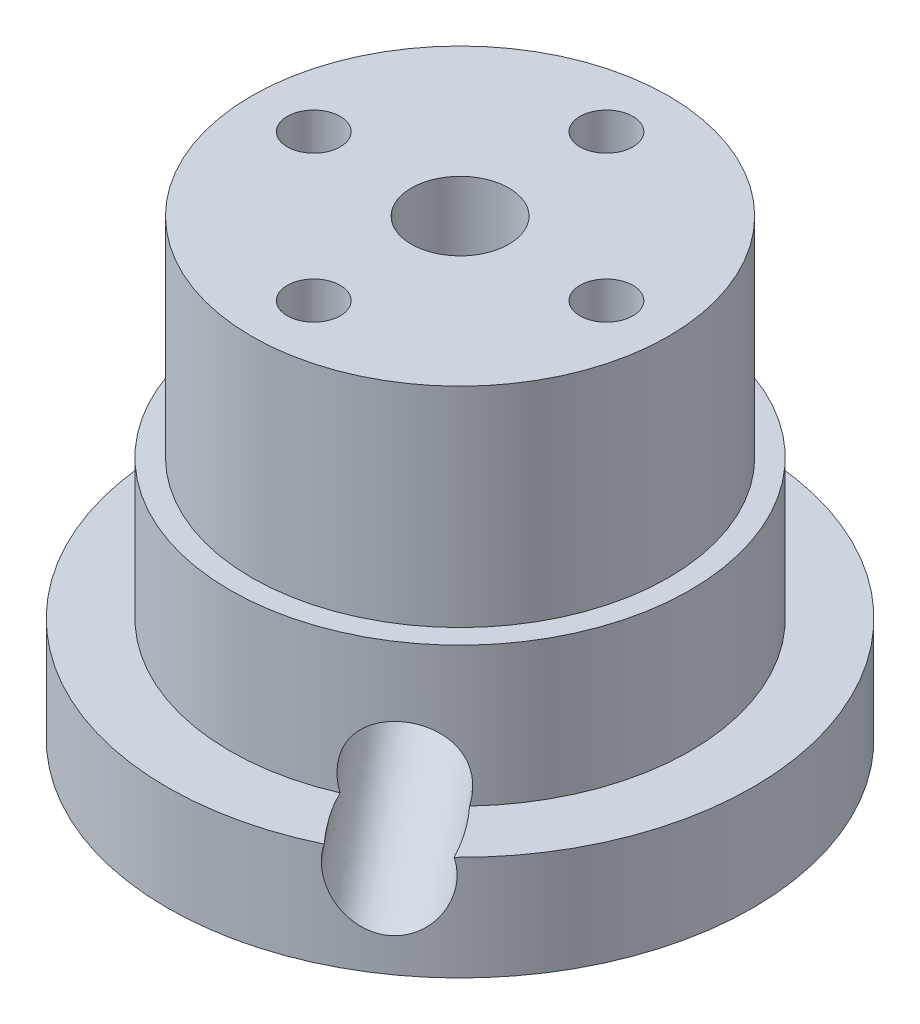
SolidWorks part; units mm, degrees
ref_plane "Alzado" through (0, 0, 0) normal (0, 0, 1) x (1, 0, 0)
ref_plane "Planta" through (0, 0, 0) normal (0, 1, 0) x (1, 0, 0)
ref_plane "Vista lateral" through (0, 0, 0) normal (1, 0, 0) x (0, 0, -1)
sketch "Croquis1" plane through (0, 0, 0) normal (0, 1, 0) x (1, 0, 0)
  circle A0 centre (0, 0) radius 21
  dimension "D1" = 42
extrude "Saliente-Extruir1" add sketch "Croquis1" along normal blind 7.5
sketch "Croquis2" plane through (0, 7.5, 0) normal (0, 1, 0) x (1, 0, 0)
  circle A0 centre (0, 0) radius 14.95
  dimension "D1" = 29.9
extrude "Saliente-Extruir2" add sketch "Croquis2" along normal blind 25
sketch "Croquis3" plane through (0, 0, 0) normal (0, -1, 0) x (1, 0, 0)
  line L0 (4, -5.5) -> (4, -8.4192) construction
  line L1 (-5.5, -4) -> (-8.4192, -4) construction
  line L2 (-4, -5.5) -> (-4, -8.4192) construction
  line L3 (-4, -8.4192) -> (-2.468, -17.8989) construction
  line L4 (4, -8.4192) -> (2.468, -17.8989) construction
  line L5 (5.5, -4) -> (8.4192, -4) construction
  line L6 (8.4192, -4) -> (17.8989, -2.468) construction
  line L7 (8.4192, 4) -> (17.8989, 2.468) construction
  line L8 (5.5, 4) -> (8.4192, 4) construction
  line L9 (4, 5.5) -> (4, 8.4192) construction
  line L10 (4, 8.4192) -> (2.468, 17.8989) construction
  line L11 (-4, 8.4192) -> (-2.468, 17.8989) construction
  line L12 (-4, 5.5) -> (-4, 8.4192) construction
  line L13 (-5.5, 4) -> (-8.4192, 4) construction
  line L14 (-8.4192, 4) -> (-17.8989, 2.468) construction
  line L15 (-8.4192, -4) -> (-17.8989, -2.468) construction
  line L16 (4, -5.5) -> (4, -8.4192) construction
  line L17 (-5.5, -4) -> (-8.4192, -4) construction
  line L18 (-4, -5.5) -> (-4, -8.4192) construction
  line L19 (-4, -8.4192) -> (-2.468, -17.8989) construction
  line L20 (4, -8.4192) -> (2.468, -17.8989) construction
  line L21 (5.5, -4) -> (8.4192, -4) construction
  line L22 (8.4192, -4) -> (17.8989, -2.468) construction
  line L23 (8.4192, 4) -> (17.8989, 2.468) construction
  line L24 (5.5, 4) -> (8.4192, 4) construction
  line L25 (4, 5.5) -> (4, 8.4192) construction
  line L26 (4, 8.4192) -> (2.468, 17.8989) construction
  line L27 (-4, 8.4192) -> (-2.468, 17.8989) construction
  line L28 (-4, 5.5) -> (-4, 8.4192) construction
  line L29 (-5.5, 4) -> (-8.4192, 4) construction
  line L30 (-8.4192, 4) -> (-17.8989, 2.468) construction
  line L31 (-8.4192, -4) -> (-17.8989, -2.468) construction
  line L32 (4.2, -5.5) -> (4.2, -8.4352)
  line L33 (4.2, -8.4352) -> (2.6654, -17.9308)
  line L34 (-4.2, -8.4352) -> (-2.6654, -17.9308)
  line L35 (-4.2, -5.5) -> (-4.2, -8.4352)
  line L36 (-5.5, -4.2) -> (-8.4352, -4.2)
  line L37 (-8.4352, -4.2) -> (-17.9308, -2.6654)
  line L38 (-8.4352, 4.2) -> (-17.9308, 2.6654)
  line L39 (-5.5, 4.2) -> (-8.4352, 4.2)
  line L40 (-4.2, 5.5) -> (-4.2, 8.4352)
  line L41 (-4.2, 8.4352) -> (-2.6654, 17.9308)
  line L42 (4.2, 8.4352) -> (2.6654, 17.9308)
  line L43 (4.2, 5.5) -> (4.2, 8.4352)
  line L44 (5.5, 4.2) -> (8.4352, 4.2)
  line L45 (8.4352, 4.2) -> (17.9308, 2.6654)
  line L46 (8.4352, -4.2) -> (17.9308, -2.6654)
  line L47 (5.5, -4.2) -> (8.4352, -4.2)
  arc A0 (-4, -5.5) -> (-5.5, -4) centre (-5.5, -5.5) ccw construction
  arc A1 (-2.468, -17.8989) -> (2.468, -17.8989) centre (0, -17.5) ccw construction
  arc A2 (5.5, -4) -> (4, -5.5) centre (5.5, -5.5) ccw construction
  arc A3 (17.8989, -2.468) -> (17.8989, 2.468) centre (17.5, 0) ccw construction
  arc A4 (4, 5.5) -> (5.5, 4) centre (5.5, 5.5) ccw construction
  arc A5 (2.468, 17.8989) -> (-2.468, 17.8989) centre (0, 17.5) ccw construction
  arc A6 (-5.5, 4) -> (-4, 5.5) centre (-5.5, 5.5) ccw construction
  arc A7 (-17.8989, 2.468) -> (-17.8989, -2.468) centre (-17.5, 0) ccw construction
  arc A8 (-4, -5.5) -> (-5.5, -4) centre (-5.5, -5.5) ccw construction
  arc A9 (-2.468, -17.8989) -> (2.468, -17.8989) centre (0, -17.5) ccw construction
  arc A10 (5.5, -4) -> (4, -5.5) centre (5.5, -5.5) ccw construction
  arc A11 (17.8989, -2.468) -> (17.8989, 2.468) centre (17.5, 0) ccw construction
  arc A12 (4, 5.5) -> (5.5, 4) centre (5.5, 5.5) ccw construction
  arc A13 (2.468, 17.8989) -> (-2.468, 17.8989) centre (0, 17.5) ccw construction
  arc A14 (-5.5, 4) -> (-4, 5.5) centre (-5.5, 5.5) ccw construction
  arc A15 (-17.8989, 2.468) -> (-17.8989, -2.468) centre (-17.5, 0) ccw construction
  arc A16 (-2.6654, -17.9308) -> (2.6654, -17.9308) centre (0, -17.5) ccw
  arc A17 (-4.2, -5.5) -> (-5.5, -4.2) centre (-5.5, -5.5) ccw
  arc A18 (-17.9308, 2.6654) -> (-17.9308, -2.6654) centre (-17.5, 0) ccw
  arc A19 (-5.5, 4.2) -> (-4.2, 5.5) centre (-5.5, 5.5) ccw
  arc A20 (2.6654, 17.9308) -> (-2.6654, 17.9308) centre (0, 17.5) ccw
  arc A21 (4.2, 5.5) -> (5.5, 4.2) centre (5.5, 5.5) ccw
  arc A22 (17.9308, -2.6654) -> (17.9308, 2.6654) centre (17.5, 0) ccw
  arc A23 (5.5, -4.2) -> (4.2, -5.5) centre (5.5, -5.5) ccw
  dimension "D1" = 0.2
extrude "Cortar-Extruir1" cut sketch "Croquis3" against normal blind 2.5 and the other way through all
sketch "Croquis4" plane through (0, 2.5, 0) normal (0, -1, 0) x (1, 0, 0)
  circle A0 centre (0, 0) radius 5.5
  dimension "D1" = 11
extrude "Cortar-Extruir2" cut sketch "Croquis4" against normal blind 1.5 and the other way through all
sketch "Croquis7" plane through (0, 7.5, 0) normal (0, 1, 0) x (1, 0, 0)
  circle A0 centre (0, 0) radius 16.5
  point P3 (0, 0)
  dimension "D1" = 33
extrude "Saliente-Extruir3" add sketch "Croquis7" along normal blind 10
sketch "Croquis6" plane through (0, 32.5, 0) normal (0, 1, 0) x (1, 0, 0)
  circle A0 centre (0, 0) radius 10.5 construction
  circle A1 centre (0, 10.5) radius 1.9
  circle A2 centre (10.5, 0) radius 1.9
  circle A3 centre (0, -10.5) radius 1.9
  circle A4 centre (-10.5, 0) radius 1.9
  point P5 (0, 0)
  point P14 (0, 0)
  dimension "D1" = 21
  dimension "D2" = 3.8
  dimension "D3" = 4
extrude "Agujeros Injertos" cut sketch "Croquis6" against normal blind 5.5 and the other way through all
ref_axis "Eje1" through (0, 34.9587, 0) along (0, -1, 0)
ref_plane "Plano1" through (0, 0, 0) normal (-0.8192, 0, 0.5736) x (0, -1, 0)
sketch "Croquis13" plane through (0, 0, 0) normal (-0.8192, 0, 0.5736) x (0, -1, 0)
  line L0 (0, 0) -> (-48.3078, 0) construction
  line L2 (-32.5, 14.95) -> (-32.5, -14.95) construction
  line L3 (-4.4667, 25.2096) -> (-10.5494, 9.8327) construction
  line L4 (-10.5494, 9.8327) -> (-18.9536, 0) construction
  line L6 (-18.9536, 0) -> (-32.5, 0) construction
  spline S0 degree 3 poles (-4.4667, 25.2096) (-10.5494, 9.8327) (-18.9536, 0) (-32.5, 0) knots 0 0 0 0 1 1 1 1
  point P2 (-32.5, 0)
  point P6 (0, 0)
  point P7 (-20.7862, 0)
  point P10 (-21.128, 1.5036)
  point P11 (-16.8355, 0)
  point P13 (-2.2238, 21.2749)
  point P14 (-2.2238, 28.7496)
  point P15 (-5.5888, 15.9839)
  point P16 (-18.9536, 0)
  point P17 (-5.9536, 25.2421)
  point P18 (-9.6334, 13.8889)
  point P19 (-4.4667, 25.2096)
  point P20 (-10.5494, 9.8327)
sweep "Cortar-Barrer2" cut path "Croquis13" circular profile diameter 7 parameters "D3"=7
sketch "Croquis27" plane through (0, 32.5, 0) normal (0, 1, 0) x (1, 0, 0)
  circle A0 centre (0, 0) radius 3.5
extrude "Cortar-Extruir3" cut sketch "Croquis27" against normal through all both and the other way through all
